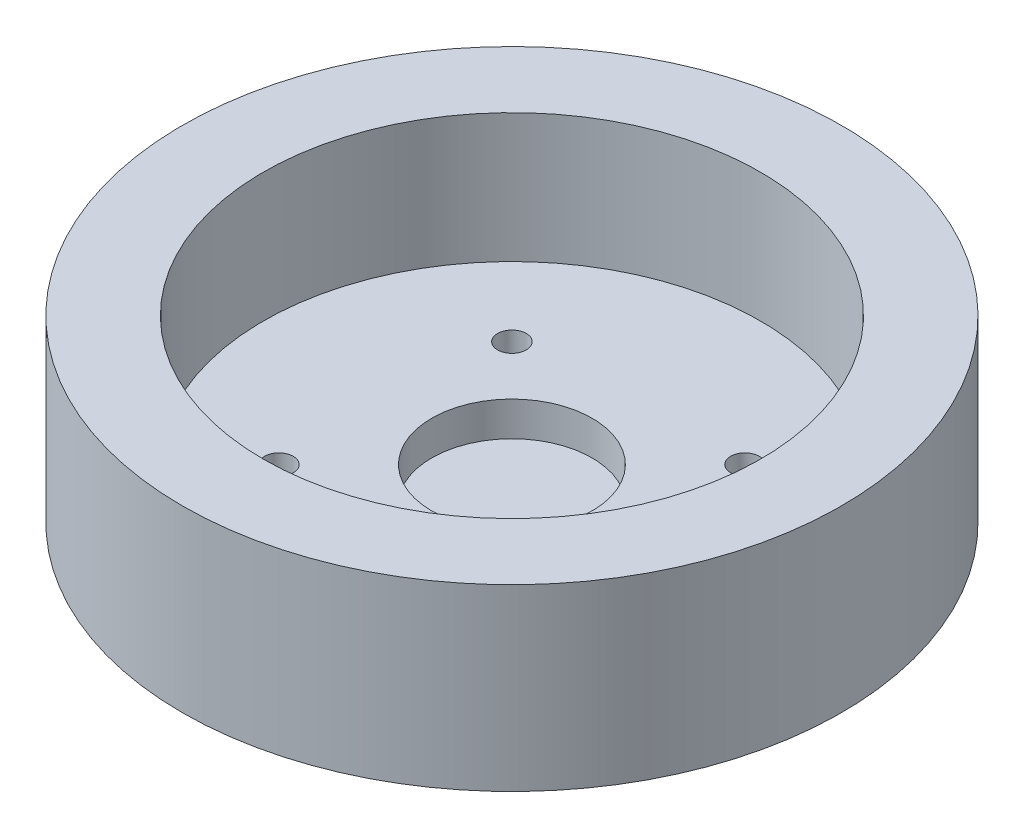
SolidWorks part; units mm, degrees
ref_plane "前视基准面" through (0, 0, 0) normal (0, 0, 1) x (1, 0, 0)
ref_plane "上视基准面" through (0, 0, 0) normal (0, 1, 0) x (1, 0, 0)
ref_plane "右视基准面" through (0, 0, 0) normal (1, 0, 0) x (0, 0, -1)
sketch "草图1" plane through (0, 0, 0) normal (0, 1, 0) x (1, 0, 0)
  circle A0 centre (0, 0) radius 16.35
  circle A1 centre (0, 0) radius 5.6
  circle A2 centre (0, 0) radius 15 construction
  circle A3 centre (0, 0) radius 23
  circle A4 centre (0, 0) radius 17.35
  dimension "D1" = 32.7
  dimension "D2" = 11.2
  dimension "D3" = 30
  dimension "D4" = 46
  dimension "D5" = 34.7
extrude "凸台-拉伸1" add sketch "草图1" along normal blind 3.5 contours A1 | A4 region at (0, 0, 0)
sketch "草图3" plane through (0, 0, 0) normal (0, 1, 0) x (1, 0, 0)
  circle A0 centre (0, 0) radius 23 construction
  circle A1 centre (0, 0) radius 23
  circle A2 centre (0, 0) radius 17.35 construction
  circle A3 centre (0, 0) radius 17.35
  dimension "D1" = 46
extrude "凸台-拉伸3" add sketch "草图3" along normal blind 12.5
sketch "草图4" plane through (0, 0, 0) normal (0, 1, 0) x (1, 0, 0)
  circle A0 centre (0, 0) radius 5.6 construction
  circle A1 centre (0, 0) radius 5.6
extrude "凸台-拉伸4" add sketch "草图4" along normal blind 1.1
sketch "草图6" plane through (0, 0, 0) normal (0, 1, 0) x (1, 0, 0)
  line L0 (-23.1107, 23.1107) -> (0, 0) construction
  line L1 (0, 0) -> (22.5537, 22.5537) construction
  circle A0 centre (0, 0) radius 16.35 construction
  circle A1 centre (0, 0) radius 16.35 construction
  circle A2 centre (0, 0) radius 17.35 construction
  circle A3 centre (0, 0) radius 17.35 construction
  circle A4 centre (8.1317, 8.1317) radius 1
  circle A5 centre (7.4246, -7.4246) radius 1
  circle A6 centre (-8.1317, -8.1317) radius 1
  circle A7 centre (-7.4246, 7.4246) radius 1
  circle A8 centre (0, 0) radius 5.6 construction
  circle A9 centre (0, 0) radius 5.6 construction
  dimension "D1" = 32.7
  dimension "D2" = 34.7
  dimension "D3" = 2
  dimension "D4" = 2
  dimension "D5" = 2
  dimension "D6" = 2
  dimension "D7" = 11.2
  dimension "D8" = 10.5
  dimension "D9" = 10.5
  dimension "D10" = 11.5
  dimension "D11" = 11.5
extrude "切除-拉伸3" cut sketch "草图6" against normal mid plane 10
sketch "草图8" plane through (0, 0, 0) normal (0, -1, 0) x (1, 0, 0)
  circle A0 centre (-8.1317, 8.1317) radius 1 construction
  circle A1 centre (-8.1317, 8.1317) radius 1 construction
  circle A2 centre (-8.1317, 8.1317) radius 1.91
  circle A3 centre (7.4246, 7.4246) radius 1.91
  circle A4 centre (-7.4246, -7.4246) radius 1.91
  circle A5 centre (8.1317, -8.1317) radius 1.91
  dimension "D1" = 3.82
  dimension "D2" = 3.82
  dimension "D3" = 3.82
  dimension "D4" = 3.82
extrude "切除-拉伸4" cut sketch "草图8" against normal blind 1.9
